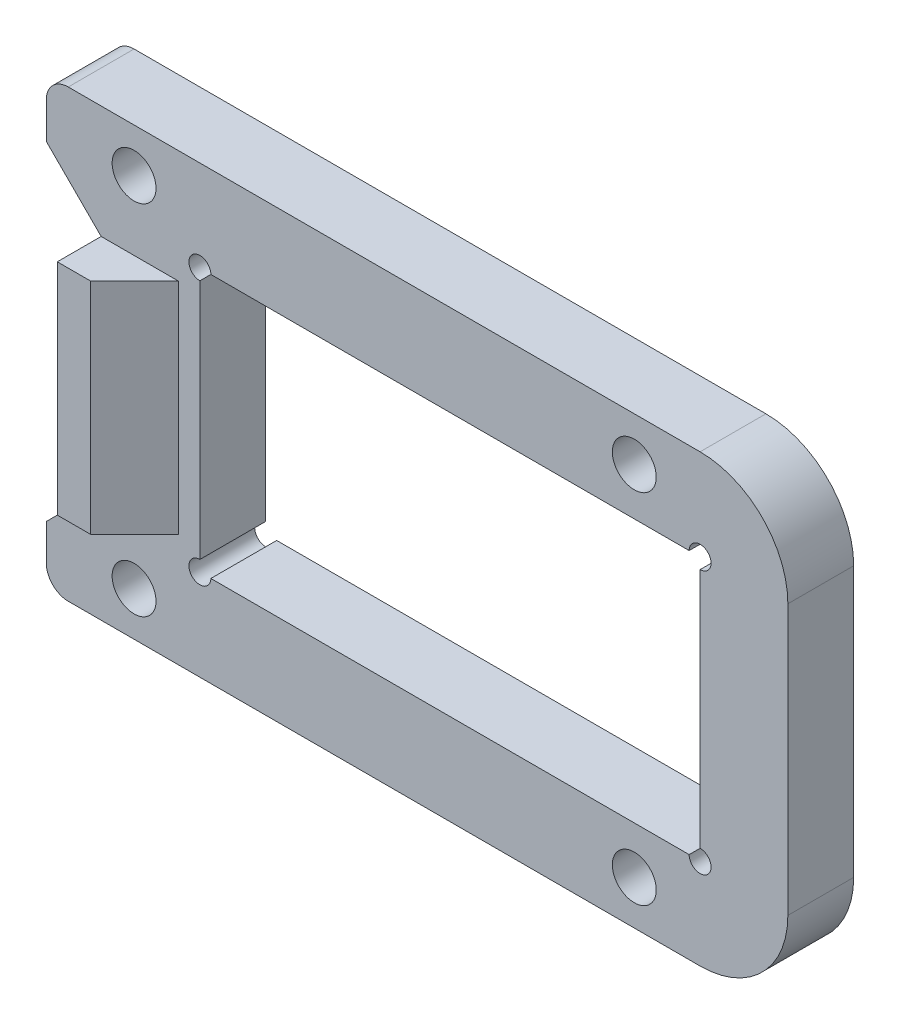
SolidWorks part; units mm, degrees
ref_plane "Front Plane" through (0, 0, 0) normal (0, 0, 1) x (1, 0, 0)
ref_plane "Top Plane" through (0, 0, 0) normal (0, 1, 0) x (1, 0, 0)
ref_plane "Right Plane" through (0, 0, 0) normal (1, 0, 0) x (0, 0, -1)
sketch "Sketch2" plane through (0, 0, 0) normal (0, 0, 1) x (1, 0, 0)
  line L3 (51.486, 0.793) -> (17.686, 0.793)
  line L6 (42.486, 10.943) -> (42.486, 6.793)
  line L7 (46.486, 10.943) -> (46.486, 6.793)
  line L8 (22.686, 10.943) -> (26.686, 10.943)
  line L13 (17.686, 10.943) -> (51.486, 10.943)
  line L14 (17.686, 10.943) -> (17.686, 0.793)
  line L15 (17.686, 0.793) -> (51.486, 0.793)
  line L16 (51.486, 10.943) -> (51.486, 0.793)
  line L17 (25.186, 6.793) -> (46.986, 6.793)
  line L18 (24.686, 6.293) -> (24.686, 0.793)
  line L19 (24.686, 0.793) -> (47.486, 0.793)
  line L20 (47.486, 6.293) -> (47.486, 0.793)
  circle A1 centre (44.486, 8.943) radius 1
  arc A3 (25.186, 6.793) -> (24.686, 6.293) centre (24.686, 6.793) ccw
  arc A4 (47.486, 6.293) -> (46.986, 6.793) centre (47.486, 6.793) ccw
  circle A5 centre (21.686, 8.943) radius 1
  dimension "D5" = 33.8
  dimension "D2" = 2
  dimension "D3" = 4
  dimension "D4" = 2
  dimension "D8" = 2
  dimension "D9" = 2
  dimension "D10" = 7
  dimension "D12" = 22.8
  dimension "D13" = 6
extrude "Boss-Extrude1" add sketch "Sketch2" along normal blind 3 contours A4 L20 L3 L16 L13 L7 L17 | A1 | L6 L17 L7 L13 A1 | A3 L17 L6 L13 L8 L14 L15 L18
mirror "Mirror1" about plane through (0, 0.793, 3) normal (0, -1, 0) of bodies 101
sketch "Sketch3" plane through (0, 0, 3) normal (0, 0, 1) x (1, 0, 0)
  line L1 (20.186, 5.793) -> (23.7012, 5.793)
  line L2 (20.186, 5.793) -> (20.186, -4.207)
  line L3 (20.186, -4.207) -> (23.7012, -4.207)
  line L4 (23.7012, 5.793) -> (23.7012, -4.207)
  line L5 (51.486, 10.943) -> (17.686, 10.943)
  line L7 (51.486, -9.357) -> (17.686, -9.357)
  line L8 (17.686, 10.943) -> (17.686, -9.357)
  point P10 (20.186, 0.793)
  point P11 (17.686, 0.793)
  dimension "D1" = 10
  dimension "D2" = 3.5153
  dimension "D3" = 0
  dimension "D4" = 2.5
extrude "Boss-Extrude2" add sketch "Sketch3" along normal blind 2 contours L4 L1 L2 L3
chamfer "Chamfer1" distance 2 angle 45 1 edges at (23.7012, 0.793, 5)
fillet "Fillet1" radius 4 2 edges at (51.486, 10.943, 1.5) (51.486, -9.357, 1.5)
fillet "Fillet2" radius 1 2 edges at (17.686, 10.943, 1.5) (17.686, -9.357, 1.5)
sketch "Sketch4" plane through (0, 0, 3) normal (0, 0, 1) x (1, 0, 0)
  line L0 (20.186, -4.207) -> (17.686, -6.707)
  line L1 (17.686, 9.943) -> (17.686, -8.357) construction
  line L2 (20.186, 5.793) -> (17.686, 8.293)
  line L3 (17.686, 8.293) -> (17.686, -6.707)
  line L4 (20.186, -4.207) -> (20.186, 5.793)
extrude "Cut-Extrude1" cut sketch "Sketch4" against normal blind 4 contours L4 L2 L3 L0
